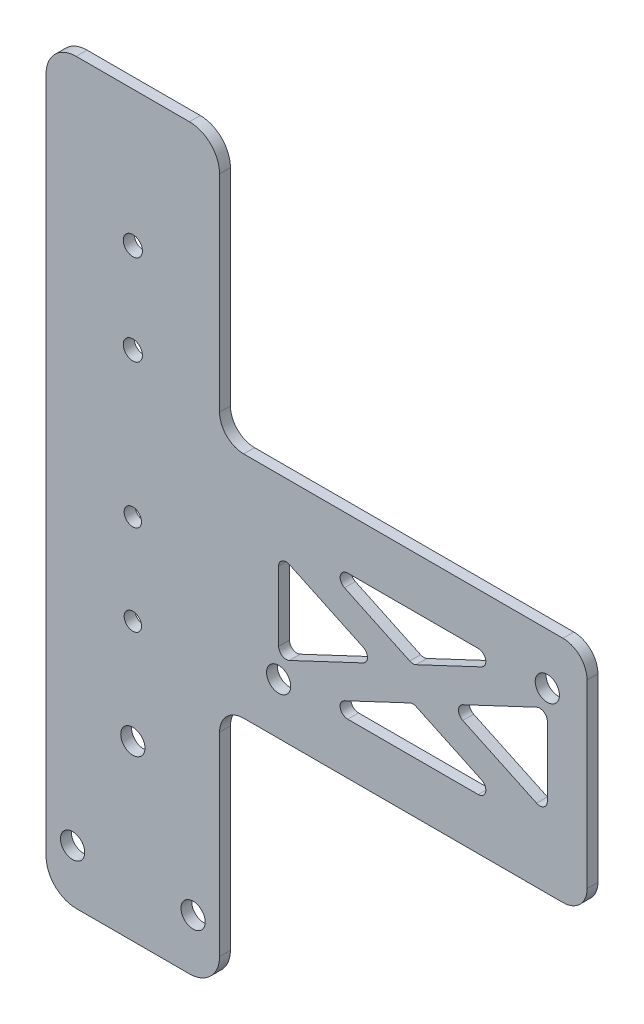
SolidWorks part; units mm, degrees
ref_plane "Front Plane" through (0, 0, 0) normal (0, 0, 1) x (1, 0, 0)
ref_plane "Top Plane" through (0, 0, 0) normal (0, 1, 0) x (1, 0, 0)
ref_plane "Right Plane" through (0, 0, 0) normal (1, 0, 0) x (0, 0, -1)
ref_plane "Plane1" through (0, 0, 1.5875) normal (0, 0, 1) x (1, 0, 0)
sketch "Sketch1" plane through (0, 0, 1.5875) normal (0, 0, 1) x (1, 0, 0)
  line L8 (18.288, -65.0875) -> (18.288, -24.13)
  line L9 (23.368, -19.05) -> (90.678, -19.05)
  line L10 (95.758, -13.97) -> (95.758, 24.13)
  line L11 (90.678, 29.21) -> (23.368, 29.21)
  line L12 (18.288, 34.29) -> (18.288, 77.7875)
  line L13 (11.938, 84.1375) -> (-11.938, 84.1375)
  line L14 (-18.288, 77.7875) -> (-18.288, -65.0875)
  line L15 (-11.938, -71.4375) -> (11.938, -71.4375)
  circle A8 centre (87.376, 18.415) radius 2.5527
  circle A9 centre (30.734, -8.255) radius 2.5527
  circle A12 centre (0, -13.0175) radius 1.8288
  circle A13 centre (0, 6.0325) radius 1.8288
  circle A14 centre (0, 36.5125) radius 2.0193
  circle A15 centre (0, 55.5625) radius 2.0193
  arc A16 (18.288, -24.13) -> (23.368, -19.05) centre (23.368, -24.13) cw
  arc A17 (90.678, -19.05) -> (95.758, -13.97) centre (90.678, -13.97) ccw
  arc A18 (95.758, 24.13) -> (90.678, 29.21) centre (90.678, 24.13) ccw
  arc A19 (23.368, 29.21) -> (18.288, 34.29) centre (23.368, 34.29) cw
  arc A20 (18.288, 77.7875) -> (11.938, 84.1375) centre (11.938, 77.7875) ccw
  arc A21 (-11.938, 84.1375) -> (-18.288, 77.7875) centre (-11.938, 77.7875) ccw
  arc A22 (-18.288, -65.0875) -> (-11.938, -71.4375) centre (-11.938, -65.0875) ccw
  arc A23 (11.938, -71.4375) -> (18.288, -65.0875) centre (11.938, -65.0875) ccw
  circle A40 centre (12.7, -60.325) radius 2.5527
  circle A41 centre (-12.7, -60.325) radius 2.5527
  circle A42 centre (0, -34.925) radius 2.5527
  dimension "D1" = 19.05
  dimension "D2" = 10.795
  dimension "D3" = 56.642
  dimension "D4" = 21.9075
extrude "Boss-Extrude1" add sketch "Sketch1" against normal blind 2.286
sketch "Sketch2" plane through (0, 0, 1.5875) normal (0, 0, 1) x (1, 0, 0)
  line L0 (95.758, 5.08) -> (19.3492, 5.08) construction
  line L1 (30.734, 18.415) -> (87.376, 18.415)
  line L2 (30.734, 18.415) -> (30.734, -8.255)
  line L3 (30.734, -8.255) -> (87.376, -8.255)
  line L4 (87.376, 18.415) -> (87.376, -8.255)
  line L5 (30.734, 18.415) -> (87.376, -8.255) construction
  line L6 (30.734, -8.255) -> (87.376, 18.415) construction
  line L7 (95.758, -13.97) -> (95.758, 24.13) construction
  line L8 (33.909, 15.24) -> (84.201, 15.24) construction
  line L9 (84.201, 15.24) -> (84.201, -5.08) construction
  line L10 (33.909, -5.08) -> (84.201, -5.08) construction
  line L11 (33.909, 15.24) -> (33.909, -5.08) construction
  line L12 (32.0865, -11.1275) -> (88.7285, 15.5425)
  line L13 (29.3815, 15.5425) -> (86.0235, -11.1275)
  line L14 (29.3815, -5.3825) -> (86.0235, 21.2875)
  line L15 (32.0865, 21.2875) -> (88.7285, -5.3825)
  line L17 (24.13, 27.305) -> (93.98, 27.305)
  line L18 (24.13, 27.305) -> (24.13, -17.145)
  line L19 (24.13, -17.145) -> (93.98, -17.145)
  line L20 (93.98, 27.305) -> (93.98, -17.145)
  line L21 (24.13, 27.305) -> (93.98, -17.145) construction
  line L22 (24.13, -17.145) -> (93.98, 27.305) construction
  point P0 (59.055, 5.08)
  point P9 (30.734, -8.255)
  point P10 (87.376, 18.415)
  point P25 (59.055, 5.08)
  dimension "D1" = 3.175
  dimension "D2" = 3.175
  dimension "D4" = 69.85
  dimension "D5" = 44.45
  dimension "D3" = 3.175
extrude "Cut-Extrude1" cut sketch "Sketch2" against normal through all contours L1 L15 L14 | L2 L14 L13 | L13 L12 L3 | L12 L15 L4 region at (59.055, 15.1398, 1.5875) region at (37.6899, 5.08, 1.5875) region at (80.4201, 5.08, 1.5875) region at (59.055, -4.9798, 1.5875)
fillet "Fillet1" radius 1.5875 12 edges at (87.376, 14.9057, 0.4445) (87.376, -4.7457, 0.4445) (66.5082, 5.08, 0.4445) (79.9228, 18.415, 0.4445) (59.055, 8.5893, 0.4445) (38.1872, 18.415, 0.4445) (51.6018, 5.08, 0.4445) (30.734, 14.9057, 0.4445) (79.9228, -8.255, 0.4445) (38.1872, -8.255, 0.4445) (59.055, 1.5707, 0.4445) (30.734, -4.7457, 0.4445)
